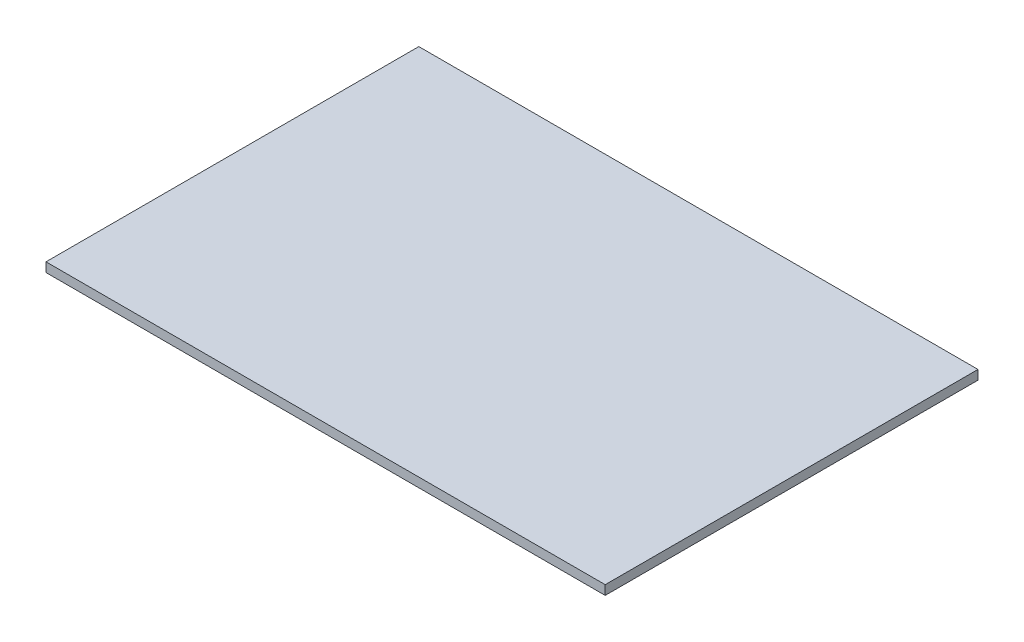
SolidWorks part; units mm, degrees
ref_plane "Front Plane" through (0, 0, 0) normal (0, 0, 1) x (1, 0, 0)
ref_plane "Top Plane" through (0, 0, 0) normal (0, 1, 0) x (1, 0, 0)
ref_plane "Right Plane" through (0, 0, 0) normal (1, 0, 0) x (0, 0, -1)
sketch "Sketch2" plane through (0, 0, 0) normal (0, 1, 0) x (1, 0, 0)
  line L1 (-95.25, -63.5) -> (95.25, -63.5)
  line L2 (-95.25, -63.5) -> (-95.25, 63.5)
  line L3 (-95.25, 63.5) -> (95.25, 63.5)
  line L4 (95.25, -63.5) -> (95.25, 63.5)
  line L5 (-95.25, -63.5) -> (95.25, 63.5) construction
  line L6 (-95.25, 63.5) -> (95.25, -63.5) construction
  point P0 (0, 0)
  dimension "D1" = 127
  dimension "D2" = 190.5
extrude "Boss-Extrude1" add sketch "Sketch2" along normal blind 3.175
